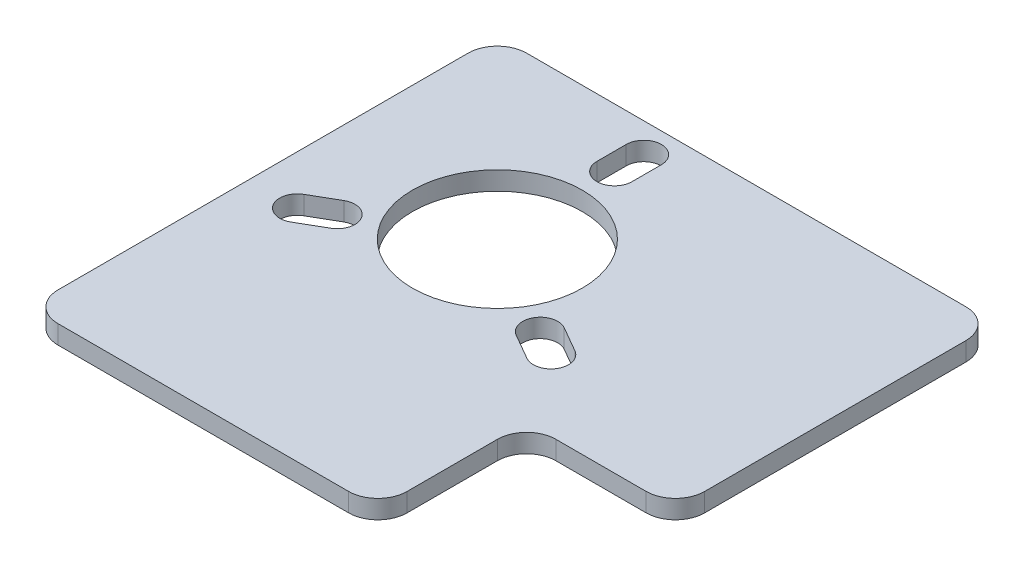
SolidWorks part; units mm, degrees
ref_plane "Front Plane" through (0, 0, 0) normal (0, 0, 1) x (1, 0, 0)
ref_plane "Top Plane" through (0, 0, 0) normal (0, 1, 0) x (1, 0, 0)
ref_plane "Right Plane" through (0, 0, 0) normal (1, 0, 0) x (0, 0, -1)
sketch "Sketch1" plane through (0, 0, 0) normal (0, 1, 0) x (1, 0, 0)
  line L1 (0, 0) -> (170, 0)
  line L2 (0, 0) -> (0, 160)
  line L3 (0, 160) -> (170, 160)
  line L4 (170, 0) -> (170, 160)
  circle A0 centre (60, 100) radius 29
  dimension "D3" = 58
  dimension "D4" = 60
  dimension "D5" = 60
  dimension "D1" = 170
  dimension "D2" = 160
extrude "Boss-Extrude1" add sketch "Sketch1" along normal blind 6.35
sketch "Sketch2" plane through (0, 6.35, 0) normal (0, 1, 0) x (1, 0, 0)
  line L1 (119.2, 0) -> (170, 0)
  line L2 (119.2, 0) -> (119.2, 50.8)
  line L3 (119.2, 50.8) -> (170, 50.8)
  line L4 (170, 0) -> (170, 50.8)
  point P5 (0, 0)
  point P6 (0, 0)
  point P9 (0, 0)
  dimension "D1" = 50.8
  dimension "D2" = 50.8
extrude "Cut-Extrude1" cut sketch "Sketch2" against normal through all
fillet "Fillet1" radius 10 6 edges at (170, 3.175, -160) (0, 3.175, -160) (119.2, 3.175, -50.8) (119.2, 3.175, 0) (170, 3.175, -50.8) (0, 3.175, 0)
sketch "Sketch3" plane through (0, 6.35, 0) normal (0, 1, 0) x (1, 0, 0)
  line L0 (60, 100) -> (16.6987, 75) construction
  line L1 (60, 100) -> (103.3013, 75) construction
  line L2 (60, 100) -> (60, 150) construction
  line L3 (60, 100) -> (139.8398, 100) construction
  line L4 (16.6987, 75) -> (25.359, 80) construction
  line L5 (13.6987, 80.1962) -> (22.359, 85.1962)
  line L6 (19.6987, 69.8038) -> (28.359, 74.8038)
  line L7 (103.3013, 75) -> (94.641, 80) construction
  line L8 (100.3013, 69.8038) -> (91.641, 74.8038)
  line L9 (106.3013, 80.1962) -> (97.641, 85.1962)
  line L10 (60, 150) -> (60, 140) construction
  line L11 (66, 150) -> (66, 140)
  line L12 (54, 150) -> (54, 140)
  arc A0 (13.6987, 80.1962) -> (19.6987, 69.8038) centre (16.6987, 75) ccw
  arc A1 (28.359, 74.8038) -> (22.359, 85.1962) centre (25.359, 80) ccw
  arc A2 (100.3013, 69.8038) -> (106.3013, 80.1962) centre (103.3013, 75) ccw
  arc A3 (97.641, 85.1962) -> (91.641, 74.8038) centre (94.641, 80) ccw
  arc A4 (66, 150) -> (54, 150) centre (60, 150) ccw
  arc A5 (54, 140) -> (66, 140) centre (60, 140) ccw
  point P3 (21.0289, 77.5)
  point P12 (98.9711, 77.5)
  point P18 (60, 145)
  dimension "D4" = 6
  dimension "D1" = 50
  dimension "D2" = 30
  dimension "D3" = 30
  dimension "D5" = 10
extrude "Cut-Extrude2" cut sketch "Sketch3" against normal through all
